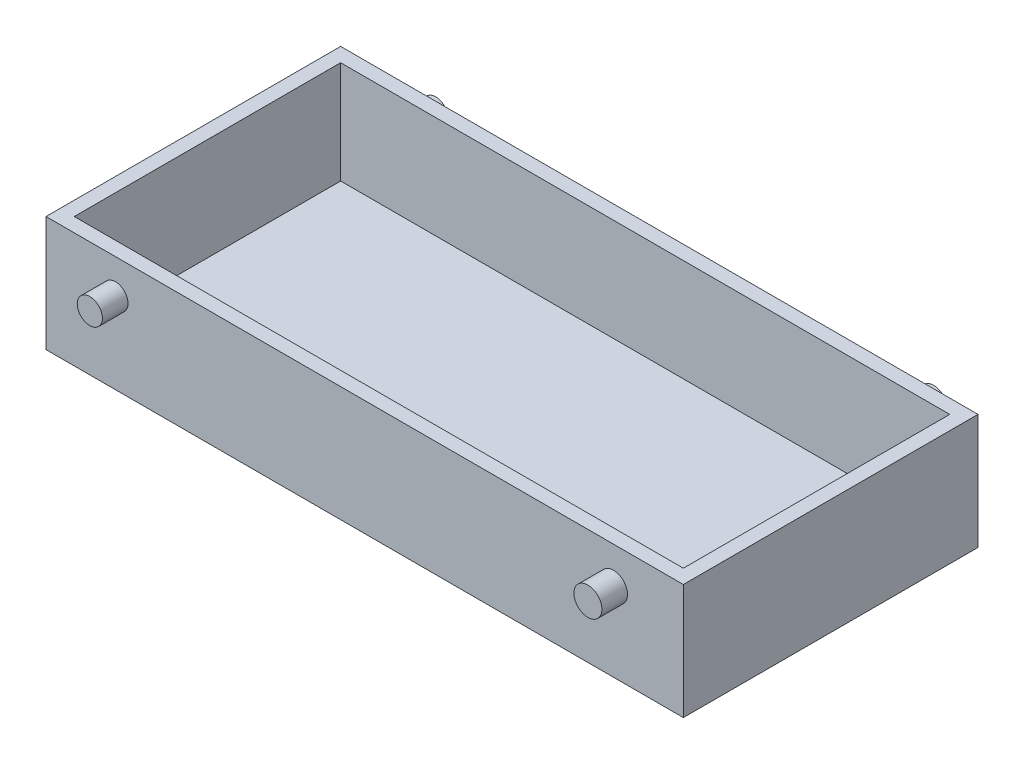
SolidWorks part; units mm, degrees
ref_plane "Front Plane" through (0, 0, 0) normal (0, 0, 1) x (1, 0, 0)
ref_plane "Top Plane" through (0, 0, 0) normal (0, 1, 0) x (1, 0, 0)
ref_plane "Right Plane" through (0, 0, 0) normal (1, 0, 0) x (0, 0, -1)
sketch "Sketch1" plane through (0, 0, 0) normal (0, 1, 0) x (1, 0, 0)
  line L0 (-157.9905, 73.0402) -> (157.9905, 73.0402)
  line L1 (-150.9903, -66.04) -> (150.9903, -66.04)
  line L2 (-150.9903, -66.04) -> (-150.9903, 66.04)
  line L3 (-150.9903, 66.04) -> (150.9903, 66.04)
  line L4 (150.9903, -66.04) -> (150.9903, 66.04)
  line L5 (0, 66.04) -> (0, -66.04) construction
  line L6 (-150.9903, 0) -> (150.9903, 0) construction
  line L7 (157.9905, -73.0402) -> (157.9905, 73.0402)
  line L8 (-157.9905, -73.0402) -> (157.9905, -73.0402)
  line L9 (-157.9905, -73.0402) -> (-157.9905, 73.0402)
  point P0 (0, 0)
  dimension "D1" = 301.9806
  dimension "D2" = 132.08
  dimension "D3" = 7.0002
extrude "Boss-Extrude1" add sketch "Sketch1" along normal blind 50.8
sketch "Sketch3" plane through (0, 0, 0) normal (0, -1, 0) x (1, 0, 0)
  line L4 (-157.9905, 73.0402) -> (-157.9905, -73.0402)
  line L5 (-157.9905, -73.0402) -> (157.9905, -73.0402)
  line L6 (157.9905, -73.0402) -> (157.9905, 73.0402)
  line L7 (157.9905, 73.0402) -> (-157.9905, 73.0402)
  line L8 (-157.9905, 73.0402) -> (-157.9905, -73.0402)
  line L9 (-157.9905, -73.0402) -> (157.9905, -73.0402)
  line L10 (157.9905, -73.0402) -> (157.9905, 73.0402)
  line L11 (157.9905, 73.0402) -> (-157.9905, 73.0402)
  dimension "D1" = 0
extrude "Boss-Extrude2" add sketch "Sketch3" along normal blind 6.35
sketch "Sketch4" plane through (0, 0, 73.0402) normal (0, 0, 1) x (1, 0, 0)
  circle A0 centre (-123.5664, 33.7741) radius 6.2425
  circle A1 centre (123.3786, 32.6474) radius 6.9483
extrude "Boss-Extrude3" add sketch "Sketch4" along normal blind 12.7
mirror "Mirror1" about plane through (0, 0, 0) normal (0, 0, 1) of "Boss-Extrude3"
